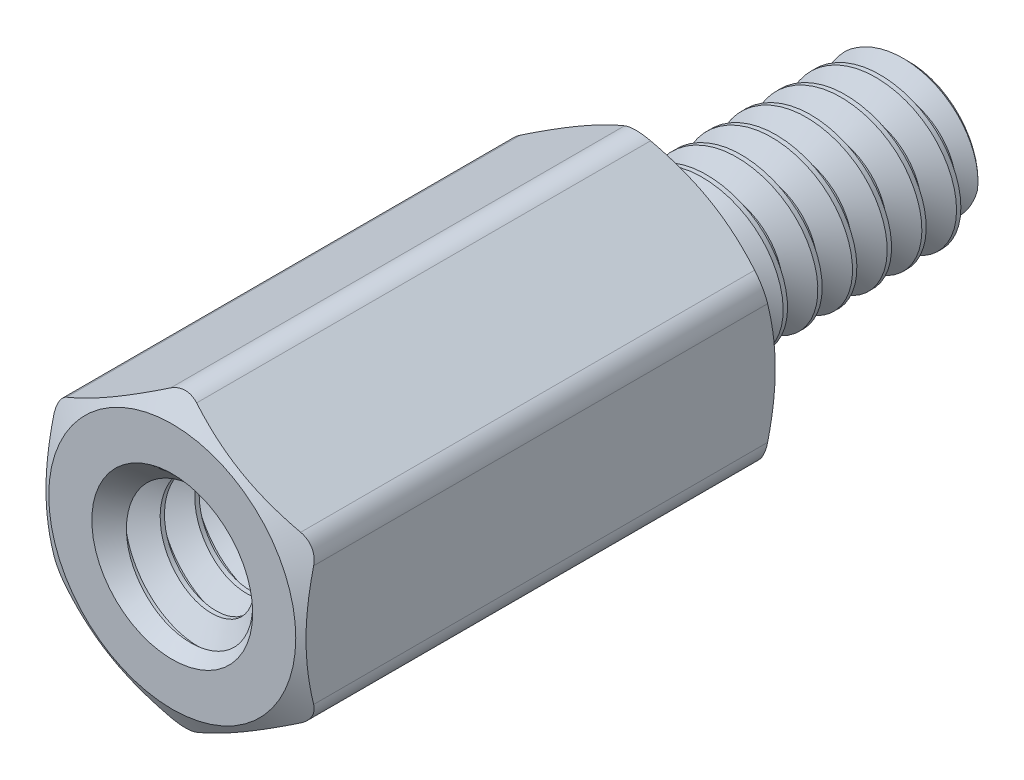
SolidWorks part; units mm, degrees
ref_plane "Front Plane" through (0, 0, 0) normal (0, 0, 1) x (1, 0, 0)
ref_plane "Top Plane" through (0, 0, 0) normal (0, 1, 0) x (1, 0, 0)
ref_plane "Right Plane" through (0, 0, 0) normal (1, 0, 0) x (0, 0, -1)
sketch "Sketch1" plane through (0, 0, 0) normal (0, 0, 1) x (1, 0, 0)
  line L1 (2.3813, 1.3748) -> (0, 2.7496)
  line L2 (0, 2.7496) -> (-2.3812, 1.3748)
  line L3 (-2.3812, 1.3748) -> (-2.3812, -1.3748)
  line L4 (-2.3812, -1.3748) -> (0, -2.7496)
  line L5 (0, -2.7496) -> (2.3813, -1.3748)
  line L6 (2.3813, -1.3748) -> (2.3813, 1.3748)
  circle A0 centre (0, 0) radius 2.3812 construction
  point P10 (0, -2.3812)
  dimension "Hex Size" = 4.7625
sketch "Sketch2" plane through (0, 0, 0) normal (1, 0, 0) x (0, 0, -1)
  line L0 (4.7625, 0) -> (-8.7312, 0) construction
  line L2 (0, 1.4224) -> (0, -1.4224) construction
  line L3 (-2.3813, 1.4224) -> (-2.3813, -1.4224) construction
  line L4 (-9.3266, 1.4911) -> (-9.0091, 0.9412) construction
  line L5 (-9.0091, 0.9412) -> (-8.6916, 1.4911) construction
  line L6 (-8.6916, 1.4911) -> (-9.3266, 1.4911) construction
  line L7 (-9.2869, 1.4224) -> (-8.7312, 1.4224) construction
  line L8 (-9.0488, 1.01) -> (-8.9694, 1.01) construction
  line L9 (-9.0091, 1.01) -> (-9.0091, 0.9412) construction
  line L10 (-9.0091, 1.4224) -> (-9.0091, 1.4911) construction
  line L11 (4.7228, 1.4911) -> (5.3578, 1.4911) construction
  line L12 (5.3578, 1.4911) -> (5.0403, 0.9412) construction
  line L13 (5.0403, 0.9412) -> (4.7228, 1.4911) construction
  line L14 (4.7625, 1.4224) -> (5.3181, 1.4224) construction
  line L15 (5.0006, 1.01) -> (5.08, 1.01) construction
  line L16 (5.0403, 1.01) -> (5.0403, 0.9412) construction
  line L17 (5.0403, 1.4224) -> (5.0403, 1.4911) construction
  line L18 (0, 2.7496) -> (-8.7312, 2.7496) construction
  point P6 (0, 0)
  point P9 (-2.3813, 0)
  dimension "Length" = 8.7312
sketch "Sketch3" plane through (0, 0, 0) normal (1, 0, 0) x (0, 0, -1)
  line L0 (-2.3813, 0) -> (4.7625, 0)
  line L1 (-2.3813, 1.4224) -> (-2.3813, -1.4224) construction
  line L2 (4.7625, 0) -> (4.7625, 1.2637)
  line L3 (4.7625, 1.2637) -> (4.6038, 1.4224)
  line L4 (4.6038, 1.4224) -> (0.8096, 1.4224)
  line L5 (0.8096, 1.4224) -> (0.5715, 1.01)
  line L6 (-2.3813, 0) -> (-2.3813, 1.2636)
  line L7 (-2.3813, 1.2636) -> (-2.54, 1.4224)
  line L8 (-2.54, 1.4224) -> (-8.5725, 1.4224)
  line L9 (-8.5725, 1.4224) -> (-8.7312, 1.5811)
  line L10 (4.6038, 0) -> (4.6038, -1.4224) construction
  line L11 (-8.7312, 1.5811) -> (-8.7312, 2.3812)
  line L12 (-8.7312, 2.3812) -> (0, 2.3812)
  line L14 (0.5715, 1.01) -> (0.1587, 1.01)
  line L15 (0, 1.1687) -> (0, 2.3812)
  arc A0 (0, 1.1687) -> (0.1587, 1.01) centre (0.1587, 1.1687) ccw
  point P5 (-8.7312, -2.3812)
  point P8 (-7.1437, -1.4224)
  point P9 (3.175, -1.4224)
  point P27 (0, 1.01)
  dimension "D4" = 0.1588
  dimension "D2" = 0.1588
  dimension "D1" = 45
  dimension "D6" = 1.5875
  dimension "D7" = 60
  dimension "D3" = 1.5875
  dimension "D5" = 0.5715
revolve "Revolve1" add sketch "Sketch3" angle 360 about L0 region at (0, 1.2491, 1.3448)
sketch "Sketch4" plane through (0, 0, 8.7312) normal (0, 0, 1) x (1, 0, 0)
  line L0 (0, 2.3812) -> (0, 1.4224) construction
  line L1 (-2.3812, 1.3748) -> (-2.3812, -1.3748)
  line L2 (-2.3812, -1.3748) -> (0, -2.7496)
  line L3 (0, -2.7496) -> (2.3812, -1.3748)
  line L4 (2.3812, -1.3748) -> (2.3812, 1.3748)
  line L5 (2.3812, 1.3748) -> (0, 2.7496)
  line L6 (0, 2.7496) -> (-2.3812, 1.3748)
  circle A0 centre (0, 0) radius 2.3812 construction
  circle A1 centre (0, 0) radius 1.9018
  circle A2 centre (0, 0) radius 2.3812 construction
  point P16 (0, 1.9018)
extrude "Boss-Extrude1" add sketch "Sketch4" against normal up to surface (8.7312 mm away) up to face at (0, 2.3812, 0)
sketch "Sketch5" plane through (0, 0, 8.7312) normal (0, 0, 1) x (1, 0, 0)
  line L0 (-0.8159, 1.1652) -> (0.8159, -1.1652) construction
  line L1 (0, 1.4224) -> (0, -1.4224) construction
  line L3 (0, -2.9435) -> (0, 2.9435) construction
  circle A0 centre (0, 0) radius 2.2622
  point P11 (0.8159, -1.1652)
  dimension "D1" = 4.5244
  dimension "D2" = 35
extrude "Cut-Extrude1" cut sketch "Sketch5" against normal through all draft 60 flip side to cut
sketch "Sketch6" plane through (0, 0, 0) normal (0, 0, -1) x (-1, 0, 0)
  circle A0 centre (0, 0) radius 2.2622
  circle A1 centre (0, 0) radius 2.2622 construction
extrude "Cut-Extrude2" cut sketch "Sketch6" against normal through all draft 60 flip side to cut
fillet "Fillet1" radius 0.4763 6 edges at (0, 2.7496, 4.3656) (-2.3812, -1.3748, 4.3656) (0, -2.7496, 4.3656) (2.3812, -1.3748, 4.3656) (2.3812, 1.3748, 4.3656) (-2.3812, 1.3748, 4.3656)
sketch "Drawing1" plane through (0, 0, 0) normal (1, 0, 0) x (0, 0, -1)
  line L0 (-8.7312, 1.4224) -> (-2.3813, 1.4224) construction
  line L1 (-2.3813, 1.4224) -> (-2.3813, -1.4224) construction
  line L2 (-2.3813, -1.4224) -> (-8.7312, -1.4224) construction
sketch "Sketch7" plane through (0, 0, 0) normal (-1, 0, 0) x (0, 0, 1)
  line L0 (-5.0006, 1.01) -> (-5.08, 1.01)
  line L1 (-5.08, 1.01) -> (-5.338, 1.4568)
  line L2 (-5.3578, 1.4911) -> (-5.0403, 0.9412) construction
  line L3 (-5.338, 1.4568) -> (-4.7427, 1.4568)
  line L4 (-5.0403, 0.9412) -> (-4.7228, 1.4911) construction
  line L5 (-4.7427, 1.4568) -> (-5.0006, 1.01)
  line L6 (-5.0403, 1.4224) -> (-5.0403, 1.4911) construction
  point P12 (-5.0403, 1.4568)
sketch "Sketch8" plane through (0, 0, -4.7625) normal (0, 0, -1) x (-1, 0, 0)
  circle A0 centre (0, 0) radius 1.4224
curve "Helix/Spiral1" pitch 0.635 height 4.6196 radius 1.4224 centre (0, 0, -4.7625) axis (0, 0, 1) start towards (0, 1, 0)
sweep "Cut-Sweep1" cut profiles "Sketch7" path "Helix/Spiral1" align with end faces yes
sketch "Sketch9" plane through (0, 0, 2.3813) normal (0, 0, 1) x (1, 0, 0)
  circle A0 centre (0, 0) radius 1.5811
extrude "Boss-Extrude2" add sketch "Sketch9" along normal up to surface (6.35 mm away) up to face at (0, 1.5811, 8.7312)
sketch "Sketch10" plane through (0, 0, 0) normal (1, 0, 0) x (0, 0, -1)
  line L0 (4.7625, 0) -> (-8.7312, 0) construction
  line L1 (-2.3813, 1.4224) -> (-8.7312, 1.4224)
  line L2 (-2.3813, 1.4224) -> (-2.3813, 0)
  line L3 (-2.3813, 0) -> (-8.7312, 0)
  line L4 (-8.7312, 1.4224) -> (-8.7312, 0)
revolve "Revolve2" add sketch "Sketch10" angle 360 about L0
sketch "Sketch11" plane through (0, 0, 8.7312) normal (0, 0, 1) x (1, 0, 0)
  circle A0 centre (0, 0) radius 1.4224
  circle A1 centre (0, 0) radius 1.4224 construction
sketch "Sketch12" plane through (0, 0, 0) normal (1, 0, 0) x (0, 0, -1)
  line L0 (-9.0488, 1.01) -> (-8.9694, 1.01)
  line L1 (-8.9694, 1.01) -> (-8.7114, 1.4568)
  line L2 (-9.0091, 0.9412) -> (-8.6916, 1.4911) construction
  line L3 (-8.7114, 1.4568) -> (-9.3067, 1.4568)
  line L4 (-9.3266, 1.4911) -> (-9.0091, 0.9412) construction
  line L5 (-9.3067, 1.4568) -> (-9.0488, 1.01)
  line L6 (-9.0091, 1.4224) -> (-9.0091, 1.4911) construction
  point P12 (-9.0091, 1.4568)
curve "Helix/Spiral2" pitch 0.635 height 6.985 radius 1.4224 centre (0, 0, 8.7312) axis (0, 0, -1) start towards (0, 1, 0)
sweep "Cut-Sweep2" cut profiles "Sketch12" path "Helix/Spiral2" align with end faces yes
combine bodies "Combine1" operation type subtract main body 113 bodies to subtract 114
sketch "Sketch13" plane through (0, 0, 8.7312) normal (0, 0, 1) x (1, 0, 0)
  circle A0 centre (0, 0) radius 1.4732
  dimension "D1" = 0.0508
extrude "Cut-Extrude3" cut sketch "Sketch13" against normal through all draft 45
equation "\"Thread Pitch (B)/8@Sketch2\"=\"Thread Pitch (B)@Sketch2\"/8"
equation "\"Thread Pitch (A)/8@Sketch2\"=\"Thread Pitch (A)@Sketch2\"/8"
equation "\"D1@Sketch5\" = \"Hex Size@Sketch1\" * .95"
equation "\"D1@Fillet1\" = \"Hex Size@Sketch1\" * .1"
equation "\"D2@Sketch3\" = \"Thread Pitch (A)@Sketch2\" * .25"
equation "\"D4@Sketch3\" = \"D2@Sketch3\""
equation "\"D6@Sketch3\" = \"Thread Pitch (A)@Sketch2\" * 2.5"
equation "\"D3@Helix/Spiral1\" = \"Thread Length (A)@Sketch2\" - \"D5@Sketch3\" * .25"
equation "\"D4@Helix/Spiral1\" = \"Thread Pitch (A)@Sketch2\""
equation "\"D3@Sketch3\" = \"Thread Pitch (B)@Sketch2\" * 2.5"
equation "\"D5@Sketch3\" = \"Thread Length (A)@Sketch2\" * .12"
equation "\"D3@Helix/Spiral2\" = \"Minimum Thread Length (B)@Sketch2\" + \"Thread Pitch (B)@Sketch2\""
equation "\"D4@Helix/Spiral2\" = \"Thread Pitch (B)@Sketch2\""
